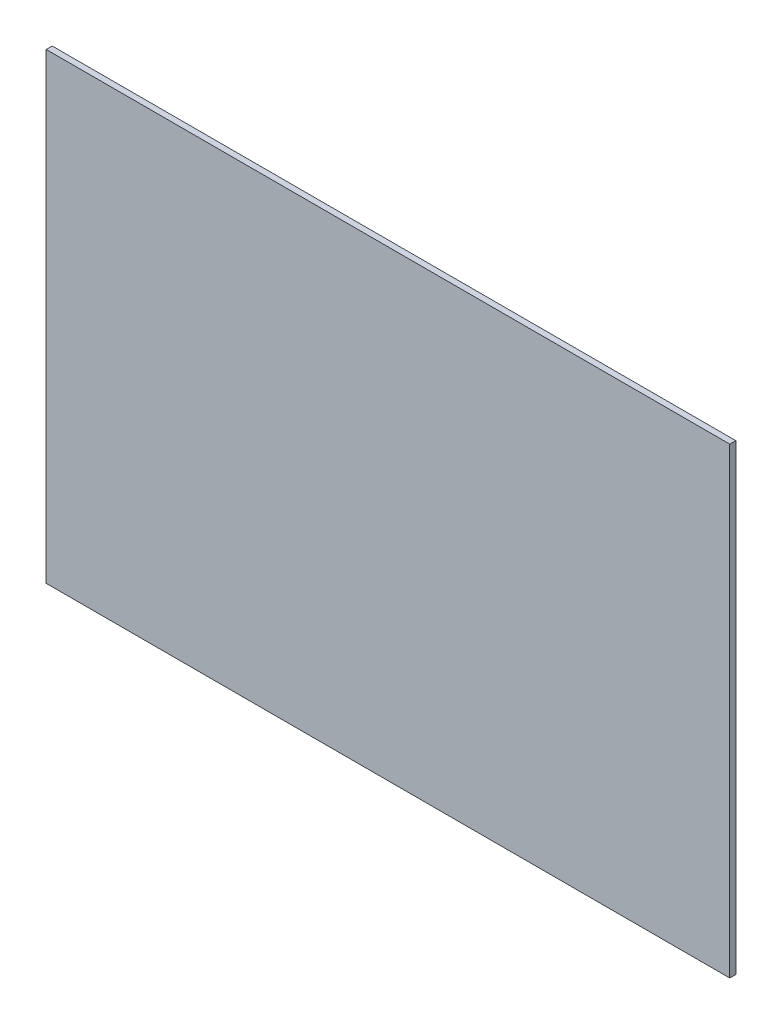
SolidWorks part; units mm, degrees
ref_plane "Front Plane" through (0, 0, 0) normal (0, 0, 1) x (1, 0, 0)
ref_plane "Top Plane" through (0, 0, 0) normal (0, 1, 0) x (1, 0, 0)
ref_plane "Right Plane" through (0, 0, 0) normal (1, 0, 0) x (0, 0, -1)
sketch "Sketch1" plane through (0, 0, 0) normal (0, 0, 1) x (1, 0, 0)
  line L1 (-170, 115) -> (170, 115)
  line L2 (-170, 115) -> (-170, -115)
  line L3 (-170, -115) -> (170, -115)
  line L4 (170, 115) -> (170, -115)
  line L5 (-170, 115) -> (170, -115) construction
  line L6 (-170, -115) -> (170, 115) construction
  point P0 (0, 0)
  dimension "D1" = 230
  dimension "D2" = 340
extrude "Boss-Extrude1" add sketch "Sketch1" along normal blind 3
